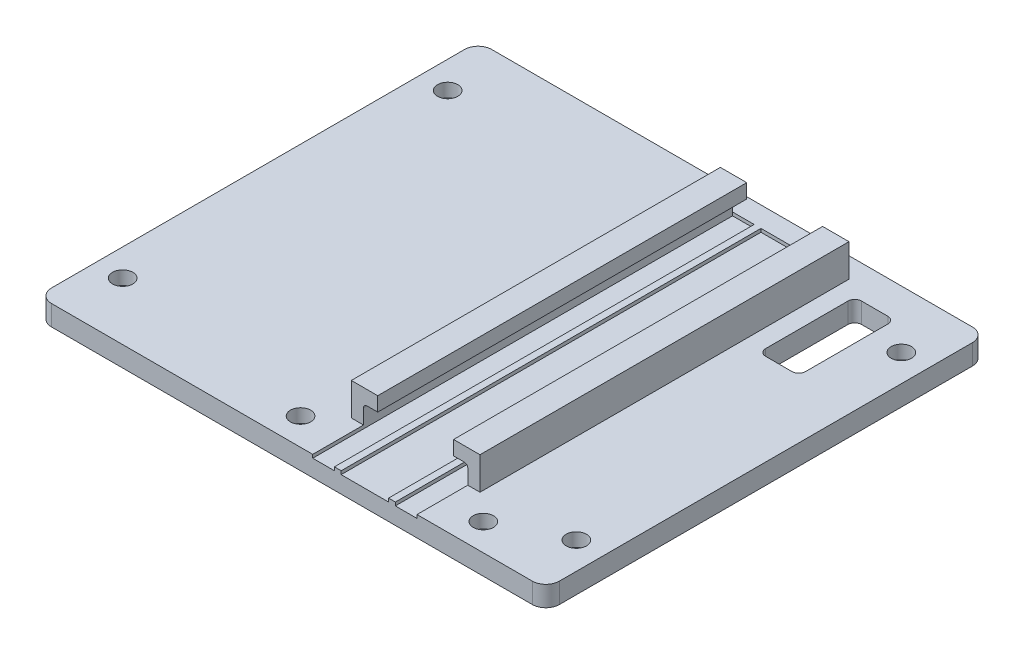
SolidWorks part; units mm, degrees
ref_plane "Alzado" through (0, 0, 0) normal (0, 0, 1) x (1, 0, 0)
ref_plane "Planta" through (0, 0, 0) normal (0, 1, 0) x (1, 0, 0)
ref_plane "Vista lateral" through (0, 0, 0) normal (1, 0, 0) x (0, 0, -1)
sketch "Croquis9" plane through (0, 0, 0) normal (0, 0, 1) x (1, 0, 0)
  line L0 (0, 17.7123) -> (0, -23.4478) construction
  line L1 (0, 10.708) -> (-22, 10.708)
  line L2 (-22, 10.708) -> (-22, 7.708)
  line L3 (-22, 7.708) -> (-19, 7.708)
  line L4 (-19, 7.708) -> (-4.5, 6.708)
  line L5 (-4.5, 6.708) -> (-4.5, -1.292)
  line L6 (-4.5, -1.292) -> (0, -1.292)
  line L7 (0, 10.708) -> (0, -1.292)
  dimension "D1" = 22
  dimension "D2" = 4.5
  dimension "D3" = 3
  dimension "D4" = 1
  dimension "D5" = 8
  dimension "D6" = 3
  dimension "D7" = 12
revolve "Revolución3" add sketch "Croquis9" angle 360 about L0
sketch "Croquis17" plane through (0, 0, 0) normal (1, 0, 0) x (0, 0, -1)
  line L0 (-4.5, -1.292) -> (4.5, -1.292) construction
  circle A0 centre (0, 4.708) radius 1.5
  dimension "D1" = 3
  dimension "D2" = 6
extrude "Cortar-Extruir7" cut sketch "Croquis17" along normal up to next
sketch "Croquis18" plane through (0, 10.708, 0) normal (0, 1, 0) x (1, 0, 0)
  line L0 (1, 2.9343) -> (1, -2.9343)
  arc A0 (1, 2.9343) -> (1, -2.9343) centre (0, 0) ccw
  dimension "D1" = 6.2
  dimension "D2" = 1
extrude "Cortar-Extruir10" cut sketch "Croquis18" against normal blind 6 from offset 3 offset against normal yes
sketch "Croquis21" plane through (0, 0, 0) normal (0, 0, 1) x (1, 0, 0)
  line L0 (0, 3.5811) -> (0, -1.3759) construction
  line L1 (0, 1.8085) -> (-3.1, 1.8085)
  line L2 (-3.1, 1.8085) -> (-3.1, -1.6716)
  line L3 (-3.1, -1.6716) -> (0, -1.6716)
  line L4 (0, 1.8085) -> (0, -1.6716)
  dimension "D1" = 3.1
revolve "Cortar-Revolución1" cut sketch "Croquis21" angle 360 about L0
chamfer "Chaflán2" distance 0.5 angle 45 1 edges at (1, 1.8085, 0)
chamfer "Chaflán1" [suppressed] distance 0.5 angle 45
sketch "Croquis22" plane through (0, 10.708, 0) normal (0, 1, 0) x (1, 0, 0)
  line L1 (-37.5, -32.5) -> (37.5, -32.5)
  line L2 (-37.5, -32.5) -> (-37.5, 32.5)
  line L3 (-37.5, 32.5) -> (37.5, 32.5)
  line L4 (37.5, -32.5) -> (37.5, 32.5)
  line L5 (-37.5, -32.5) -> (37.5, 32.5) construction
  line L6 (-37.5, 32.5) -> (37.5, -32.5) construction
  point P0 (0, 0)
  dimension "D1" = 65
  dimension "D2" = 75
extrude "Saliente-Extruir1" add sketch "Croquis22" against normal up to surface (3 mm away) up to face at (0, 7.708, 19)
fillet "Redondeo1" radius 2 4 edges at (-37.5, 9.208, -32.5) (37.5, 9.208, -32.5) (37.5, 9.208, 32.5) (-37.5, 9.208, 32.5)
sketch "Croquis23" plane through (0, 10.708, 0) normal (0, 1, 0) x (1, 0, 0)
  circle A0 centre (-33.5, 24) radius 1.5
  circle A1 centre (-33.5, -24) radius 1.5
  circle A2 centre (33.5, -24) radius 1.5
  circle A3 centre (33.5, 24) radius 1.5
  dimension "D1" = 3
  dimension "D4" = 48
  dimension "D3" = 33.5
  dimension "D2" = 67
  dimension "D5" = 24
extrude "Cortar-Extruir11" cut sketch "Croquis23" against normal blind 2
sketch "Croquis24" plane through (0, 10.708, 0) normal (0, 1, 0) x (1, 0, 0)
  line L1 (3.27, 29.5) -> (18.27, 29.5)
  line L2 (3.27, 29.5) -> (3.27, -32.5)
  line L3 (3.27, -32.5) -> (18.27, -32.5)
  line L4 (18.27, 29.5) -> (18.27, -32.5)
  line L5 (6.27, 29.5) -> (7.27, 29.5)
  line L6 (6.27, 29.5) -> (6.27, -32.5)
  line L7 (6.27, -32.5) -> (7.27, -32.5)
  line L8 (7.27, 29.5) -> (7.27, -32.5)
  line L9 (14.27, 29.5) -> (15.27, 29.5)
  line L10 (14.27, 29.5) -> (14.27, -32.5)
  line L11 (14.27, -32.5) -> (15.27, -32.5)
  line L12 (15.27, 29.5) -> (15.27, -32.5)
  line L13 (35.5, 32.5) -> (-35.5, 32.5) construction
  line L14 (-35.5, -32.5) -> (35.5, -32.5) construction
  dimension "D1" = 3
  dimension "D2" = 15
  dimension "D3" = 1
  dimension "D4" = 1
  dimension "D5" = 3.27
  dimension "D6" = 3
  dimension "D7" = 3
extrude "Cortar-Extruir12" cut sketch "Croquis24" against normal blind 0.5 contours L6 L1 L2 L3 | L10 L1 L8 L3 | L1 L12 L3 L4 region at (4.77, 10.708, 1.5) region at (10.77, 10.708, 1.5) region at (16.77, 10.708, 1.5)
sketch "Croquis25" plane through (0, 10.708, 0) normal (0, 1, 0) x (1, 0, 0)
  line L0 (3.27, 29.5) -> (3.27, -32.5) construction
  line L1 (18.27, 29.5) -> (18.27, -32.5) construction
  line L3 (-35.5, -32.5) -> (3.27, -32.5) construction
  circle A0 centre (-2.73, -28.5) radius 1.5
  circle A1 centre (24.27, -28.5) radius 1.5
  circle A2 centre (33.5, -24) radius 1.5 construction
  circle A3 centre (33.5, -24) radius 1.5 construction
  dimension "D2" = 6
  dimension "D1" = 6
  dimension "D4" = 4
extrude "Cortar-Extruir13" cut sketch "Croquis25" against normal blind 2
sketch "Croquis26" plane through (0, 10.708, 0) normal (0, 1, 0) x (1, 0, 0)
  line L1 (22.988, 27.6308) -> (28.8765, 27.6308)
  line L2 (22.988, 27.6308) -> (22.988, 13.4757)
  line L3 (22.988, 13.4757) -> (28.8765, 13.4757)
  line L4 (28.8765, 27.6308) -> (28.8765, 13.4757)
extrude "Cortar-Extruir14" cut sketch "Croquis26" against normal blind 10
sketch "Croquis30" plane through (0, 0, 32.5) normal (0, 0, 1) x (1, 0, 0)
  line L0 (3.27, 10.708) -> (1.27, 10.708)
  line L1 (1.27, 10.708) -> (1.27, 15.508)
  line L2 (1.27, 15.508) -> (5.17, 15.508)
  line L3 (5.17, 15.508) -> (5.17, 13.408)
  line L4 (5.17, 13.408) -> (3.27, 13.408)
  line L5 (3.27, 13.408) -> (3.27, 10.708)
  line L6 (18.27, 10.708) -> (20.27, 10.708)
  line L7 (18.27, 10.708) -> (35.5, 10.708) construction
  line L8 (20.27, 10.708) -> (20.27, 15.508)
  line L9 (20.27, 15.508) -> (16.37, 15.508)
  line L10 (16.37, 15.508) -> (16.37, 13.408)
  line L11 (16.37, 13.408) -> (18.27, 13.408)
  line L12 (18.27, 13.408) -> (18.27, 10.708)
  point P12 (0, 0)
  point P18 (0, 0)
  point P20 (0, 0)
  dimension "D1" = 1.9
  dimension "D2" = 4.8
  dimension "D3" = 2
  dimension "D4" = 2.7
extrude "Saliente-Extruir2" add sketch "Croquis30" against normal up to surface (62 mm away) from offset 7.5 up to face at (4.77, 10.458, -29.5) offset against normal yes
sketch "Croquis31" plane through (0, 0, 32.5) normal (0, 0, 1) x (1, 0, 0)
  line L0 (3.27, 13.408) -> (5.17, 13.408) construction
  line L1 (3.27, 10.208) -> (3.07, 10.208)
  line L2 (3.27, 10.208) -> (3.27, 13.408)
  line L3 (3.27, 13.408) -> (3.07, 13.408)
  line L4 (3.07, 10.208) -> (3.07, 13.408)
  line L5 (18.27, 10.208) -> (18.47, 10.208)
  line L6 (18.27, 10.208) -> (18.27, 13.408)
  line L7 (18.27, 13.408) -> (18.47, 13.408)
  line L8 (18.47, 10.208) -> (18.47, 13.408)
  line L9 (16.37, 13.408) -> (18.27, 13.408) construction
  point P12 (0, 0)
  dimension "D1" = 0.2
  dimension "D2" = 0.2
extrude "Cortar-Extruir17" cut sketch "Croquis31" against normal up to surface (62 mm away) up to face at (4.77, 10.458, -29.5)
fillet "Redondeo2" radius 0.5 2 edges at (18.47, 13.408, -2.25) (3.07, 13.408, -2.25)
fillet "Redondeo3" radius 1 4 edges at (28.8765, 9.208, -13.4757) (22.988, 9.208, -13.4757) (22.988, 9.208, -27.6308) (28.8765, 9.208, -27.6308)
